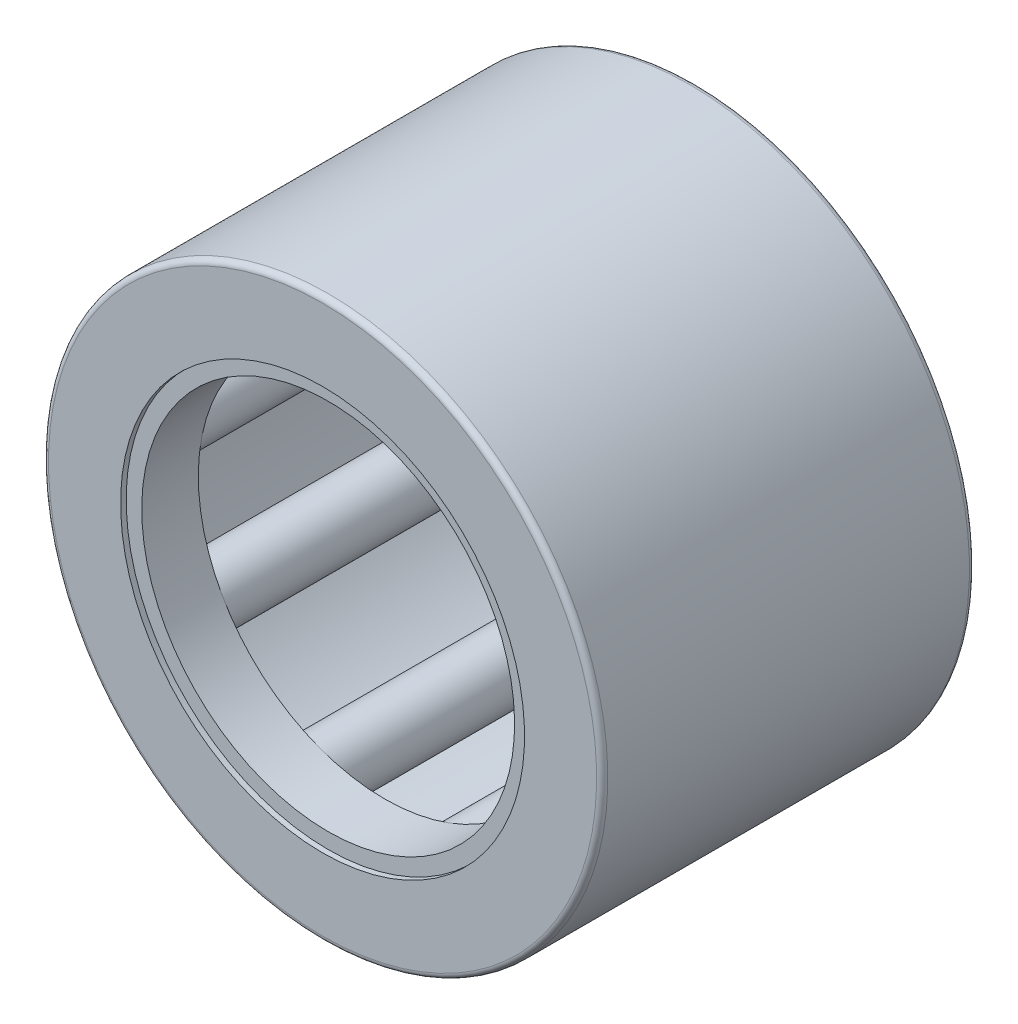
SolidWorks part; units mm, degrees
ref_plane "Front Plane" through (0, 0, 0) normal (0, 0, 1) x (1, 0, 0)
ref_plane "Top Plane" through (0, 0, 0) normal (0, 1, 0) x (1, 0, 0)
ref_plane "Right Plane" through (0, 0, 0) normal (1, 0, 0) x (0, 0, -1)
sketch "Sketch1" plane through (0, 0, 0) normal (1, 0, 0) x (0, 0, -1)
  line L0 (-4, 0) -> (4, 0) construction
  line L1 (0, 0) -> (0, 6) construction
  line L2 (-4, 0) -> (-4, 6) construction
  line L3 (-4, 6) -> (4, 6)
  line L4 (4, 6) -> (4, 0) construction
  line L5 (4, 0) -> (3.3333, 0) construction
  line L6 (3.3333, 0) -> (3.3333, 5.3333) construction
  line L7 (3.3333, 5.3333) -> (-3.3333, 5.3333)
  line L8 (-3.3333, 5.3333) -> (-3.3333, 0) construction
  line L9 (-3.3333, 0) -> (-4, 0) construction
  line L10 (-4, 6) -> (-4, 4.3333)
  line L11 (-4, 4.3333) -> (-3.3333, 4.3333)
  line L12 (-3.3333, 4.3333) -> (-3.3333, 5.3333)
  line L13 (3.3333, 6) -> (3.3333, 5.3333) construction
  line L14 (3.3333, 5.3333) -> (3.3333, 4.3333)
  line L15 (3.3333, 4.3333) -> (4, 4.3333)
  line L16 (4, 4.3333) -> (4, 6)
  line L17 (3.3333, 5.3333) -> (3.3333, 4.6667) construction
  line L18 (3.3333, 4.6667) -> (3.3333, 4) construction
  line L19 (3.3333, -5.3333) -> (3.3333, -4.6667) construction
  line L20 (3.3333, -6) -> (3.3333, -5.3333) construction
  line L21 (4, -4.3333) -> (4, -6) construction
  line L22 (3.3333, -4.3333) -> (4, -4.3333) construction
  line L23 (3.3333, -5.3333) -> (3.3333, -4.3333) construction
  line L24 (-3.3333, -4.3333) -> (-3.3333, -5.3333) construction
  line L25 (-4, -4.3333) -> (-3.3333, -4.3333) construction
  line L26 (-4, -6) -> (-4, -4.3333) construction
  line L27 (3.3333, -5.3333) -> (-3.3333, -5.3333) construction
  line L28 (-4, -6) -> (4, -6) construction
  point P4 (0, 4)
  dimension "C | Width" = 8
  dimension "Fw | ID" = 8
  dimension "D | OD" = 12
sketch "Sketch7" plane through (0, 0, 0) normal (1, 0, 0) x (0, 0, -1)
  line L0 (-4, 6) -> (-4, 4.3333) construction
  line L1 (-4, 4.3333) -> (-3.3333, 4.3333) construction
  line L2 (-3.3333, 4.3333) -> (-3.3333, 5.3333) construction
  line L3 (3.3333, 5.3333) -> (-3.3333, 5.3333) construction
  line L4 (3.3333, 5.3333) -> (3.3333, 4.3333) construction
  line L5 (3.3333, 4.3333) -> (4, 4.3333) construction
  line L6 (4, 4.3333) -> (4, 6) construction
  line L8 (-4, 6) -> (4, 6) construction
  line L9 (-4, 6) -> (-4, 4.3333)
  line L10 (-4, 4.3333) -> (-3.3333, 4.3333)
  line L13 (-3.3333, 4.3333) -> (-3.3333, 5.3333)
  line L16 (3.3333, 5.3333) -> (-3.3333, 5.3333)
  line L17 (3.3333, 5.3333) -> (3.3333, 4.3333)
  line L18 (3.3333, 4.3333) -> (4, 4.3333)
  line L19 (4, 4.3333) -> (4, 6)
  line L20 (-4, 6) -> (4, 6)
revolve "Revolve1" add sketch "Sketch7" angle 360 about L0
sketch "Sketch2" plane through (0, 0, 0) normal (1, 0, 0) x (0, 0, -1)
  line L0 (-4, 4.3333) -> (-3.3333, 4.3333) construction
  line L1 (-2.6667, 4.6667) -> (2.6667, 4.6667) construction
  line L2 (-2.6667, 4.6667) -> (-2.6667, 5.3333) construction
  line L3 (-2.6667, 5.3333) -> (2.6667, 5.3333)
  line L4 (2.6667, 4.6667) -> (2.6667, 5.3333) construction
  line L5 (3.3333, 4.3333) -> (4, 4.3333) construction
  line L6 (-3.3333, 4.6667) -> (-2.6667, 4.6667) construction
  line L7 (2.6667, 4.6667) -> (3.3333, 4.6667) construction
  line L8 (4, 6) -> (4, 0) construction
  line L9 (-2.6667, 4.8333) -> (-2.6667, 4.5) construction
  line L10 (-3.3333, 4.6667) -> (-3.3333, 4.3333) construction
  line L11 (-2.6667, 5.3333) -> (-2.6667, 4.8333)
  line L12 (2.6667, 5.3333) -> (2.6667, 4.8333)
  line L13 (2.6667, 4.8333) -> (-2.6667, 4.8333)
  line L14 (0, 5.3333) -> (0, 4) construction
  line L16 (-2.6667, 4.5) -> (-3.3333, 4.5) construction
  line L17 (0, 0) -> (4, 0) construction
  line L18 (-2.6667, -4.5) -> (-3.3333, -4.5) construction
  line L19 (0, -5.3333) -> (0, -4) construction
  line L20 (-3.3333, -4.6667) -> (-3.3333, -4.3333) construction
  line L21 (-2.6667, -4.8333) -> (-2.6667, -4.5) construction
  line L22 (2.6667, -4.6667) -> (3.3333, -4.6667) construction
  line L23 (-3.3333, -4.6667) -> (-2.6667, -4.6667) construction
  line L24 (2.6667, -4.6667) -> (2.6667, -5.3333) construction
  line L25 (-2.6667, -4.6667) -> (-2.6667, -5.3333) construction
  line L26 (-2.6667, -4.6667) -> (2.6667, -4.6667) construction
  line L27 (2.6667, -4.8333) -> (-2.6667, -4.8333) construction
  line L28 (2.6667, -5.3333) -> (2.6667, -4.8333) construction
  line L29 (-2.6667, -5.3333) -> (-2.6667, -4.8333) construction
  line L30 (-2.6667, -5.3333) -> (2.6667, -5.3333) construction
  line L33 (3.3333, 5.3333) -> (-3.3333, 5.3333) construction
  line L34 (3.3333, 5.3333) -> (3.3333, 4.3333) construction
  line L35 (-3.3333, 4.3333) -> (-3.3333, 5.3333) construction
  line L36 (0, 0) -> (0, 6) construction
  point P16 (0, 4.6667)
revolve "Revolve2" add sketch "Sketch2" angle 360 about L1
sketch "Sketch3" plane through (0, 0, 0) normal (1, 0, 0) x (0, 0, -1)
  line L1 (-3.3333, 4.6667) -> (3.3333, 4.6667)
  line L2 (-3.3333, 4.6667) -> (-3.3333, 4.8333)
  line L3 (-3.3333, 4.8333) -> (3.3333, 4.8333)
  line L4 (3.3333, 4.6667) -> (3.3333, 4.8333)
  line L5 (0, 0) -> (4, 0) construction
  line L7 (3.3333, -4.6667) -> (3.3333, -4.8333) construction
  line L8 (-3.3333, -4.8333) -> (3.3333, -4.8333) construction
  line L9 (-3.3333, -4.6667) -> (-3.3333, -4.8333) construction
  line L10 (-3.3333, -4.6667) -> (3.3333, -4.6667) construction
  line L11 (3.3333, 5.3333) -> (3.3333, 4.3333) construction
  line L12 (4, 6) -> (4, 0) construction
revolve "Revolve3" add sketch "Sketch3" angle 360 about L1
ref_axis "Axis1" through (0, 4.3333, 4) along (0, 1, 0)
pattern_circular "CirPattern1" count 9 every 40 about axis through (0, 0, 4) along (0, 0, -1) of bodies 166 167
fillet "Fillet1" radius 0.12 2 edges at (0, -6, -4) (0, -6, 4)
sketch "Sketch4" plane through (0, 0, 0) normal (1, 0, 0) x (0, 0, -1)
  line L0 (2.6667, 5.3333) -> (2.6667, 4.8333) construction
  line L1 (3.88, 4) -> (2.6667, 4)
  line L2 (3.88, 4) -> (3.88, 4.3333)
  line L3 (3.88, 4.3333) -> (2.6667, 4.3333)
  line L4 (2.6667, 4) -> (2.6667, 4.3333)
  line L7 (3.3333, 4.3333) -> (4, 4.3333) construction
  line L8 (3.88, -6) -> (3.88, 6) construction
revolve "Revolve4" add sketch "Sketch4" angle 360 about L0
sketch "Sketch5" plane through (0, 0, 0) normal (1, 0, 0) x (0, 0, -1)
  line L0 (-3.88, 6) -> (-3.88, -6) construction
  line L1 (-2.6667, 4) -> (-3.88, 4)
  line L2 (-2.6667, 4) -> (-2.6667, 4.3333)
  line L3 (-2.6667, 4.3333) -> (-3.88, 4.3333)
  line L4 (-3.88, 4) -> (-3.88, 4.3333)
  line L5 (-2.6667, 5.3333) -> (-2.6667, 4.8333) construction
  line L6 (-4, 4.3333) -> (-3.3333, 4.3333) construction
revolve "Revolve5" add sketch "Sketch5" angle 360 about L0
sketch "Front View" plane through (0, 0, 0) normal (0, 0, 1) x (1, 0, 0)
  circle A0 centre (0, 0) radius 4 construction
  circle A1 centre (0, 0) radius 6 construction
  dimension "ID" = 8
  dimension "OD" = 12
sketch "Right View" plane through (0, 0, 0) normal (1, 0, 0) x (0, 0, -1)
  line L0 (-4, 6) -> (4, 6) construction
  line L1 (-4, 6) -> (4, 6) construction
  line L2 (0, 0) -> (0, 6) construction
  point P4 (0, 6)
  dimension "Width" = 8
ref_axis "Axis2" through (0, 0, -3.88) along (0, 0, 1)
ref_plane "Plane1" through (0, 0, -4) normal (0, 0, -1) x (-1, 0, 0)
ref_plane "Plane2" through (0, 0, 4) normal (0, 0, 1) x (1, 0, 0)
equation "\"Rollers@CirPattern1\"  = \"OD@Sketch1\"*.75"
equation "\"D1@Fillet1\" = \"D | OD@Sketch1\" * .01"
equation "\"Angle@CirPattern1\"=360 / \"Rollers@CirPattern1\""
equation "\"ID@Front View\" = \"Fw | ID@Sketch1\""
equation "\"OD@Front View\" = \"D | OD@Sketch1\""
equation "\"Width@Right View\" = \"C | Width@Sketch1\""
